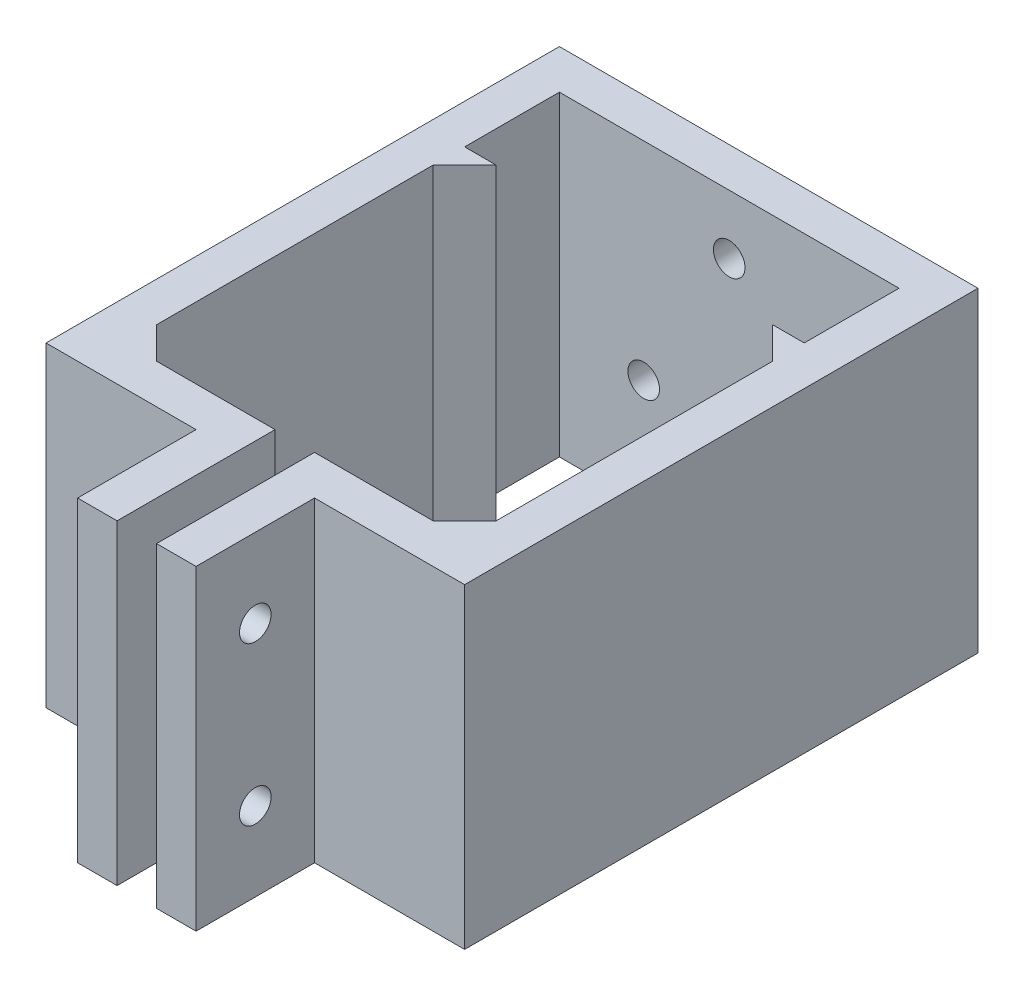
SolidWorks part; units mm, degrees
ref_plane "Спереди" through (0, 0, 0) normal (0, 0, 1) x (1, 0, 0)
ref_plane "Сверху" through (0, 0, 0) normal (0, 1, 0) x (1, 0, 0)
ref_plane "Справа" through (0, 0, 0) normal (1, 0, 0) x (0, 0, -1)
sketch "Эскиз1" plane through (0, 0, 0) normal (0, 1, 0) x (1, 0, 0)
  line L0 (0, 0) -> (0, 65)
  line L1 (0, 65) -> (53, 65)
  line L2 (53, 65) -> (53, 0)
  line L3 (53, 0) -> (34, 0)
  line L4 (34, 0) -> (34, -15)
  line L5 (34, -15) -> (29, -15)
  line L6 (29, -15) -> (29, 5)
  line L7 (29, 5) -> (48, 5)
  line L8 (48, 5) -> (48, 60)
  line L9 (48, 60) -> (5, 60)
  line L10 (5, 60) -> (5, 5)
  line L11 (5, 5) -> (24, 5)
  line L12 (24, 5) -> (24, -15)
  line L13 (24, -15) -> (19, -15)
  line L14 (19, -15) -> (19, 0)
  line L15 (19, 0) -> (0, 0)
  dimension "D1" = 55
  dimension "D2" = 5
  dimension "D3" = 43
  dimension "D4" = 5
  dimension "D5" = 5
  dimension "D6" = 53
  dimension "D7" = 5
  dimension "D8" = 15
extrude "main" add sketch "Эскиз1" along normal blind 40
chamfer "Фаска1" distance 4 angle 45 2 edges at (48, 20, -5) (5, 20, -5)
sketch "Эскиз2" plane through (0, 0, -65) normal (0, 0, -1) x (-1, 0, 0)
  line L0 (-26.5, 40) -> (-26.5, 0) construction
  line L1 (-53, 40) -> (0, 40) construction
  line L2 (-53, 0) -> (0, 0) construction
  line L3 (-53, 20) -> (0, 20) construction
  line L4 (-53, 40) -> (-53, 0) construction
  line L5 (0, 40) -> (0, 0) construction
  line L6 (-26.5, 20) -> (-37.3253, 13.75) construction
  circle A0 centre (-26.5, 20) radius 12.5 construction
  circle A1 centre (-26.5, 32.5) radius 2
  circle A2 centre (-37.3253, 13.75) radius 2
  circle A3 centre (-15.6747, 13.75) radius 2
  point P12 (-26.5, 20)
  point P15 (-26.5, 32.5)
  dimension "D1" = 25
  dimension "D2" = 4
  dimension "D3" = 120
extrude "holes" cut sketch "Эскиз2" against normal up to next
sketch "Эскиз3" plane through (0, 0, 0) normal (0, 1, 0) x (1, 0, 0)
  line L0 (5, 44) -> (5, 48)
  line L1 (5, 9) -> (5, 60) construction
  line L2 (5, 48) -> (9, 48)
  line L3 (9, 48) -> (5, 44)
  line L4 (24, 5) -> (9, 5) construction
  line L5 (26.5, 65) -> (26.5, 5) construction
  line L6 (53, 65) -> (0, 65) construction
  line L7 (44, 5) -> (29, 5) construction
  line L8 (44, 48) -> (48, 44)
  line L9 (48, 48) -> (44, 48)
  line L10 (48, 44) -> (48, 48)
  dimension "D1" = 4
  dimension "D2" = 43
extrude "Вытянуть3" add sketch "Эскиз3" along normal blind 40
sketch "Эскиз4" plane through (34, 0, 0) normal (1, 0, 0) x (0, 0, -1)
  line L0 (-7.5, 40) -> (-7.5, 0) construction
  line L1 (-15, 40) -> (0, 40) construction
  line L2 (-15, 0) -> (0, 0) construction
  circle A0 centre (-7.5, 10) radius 2
  circle A1 centre (-7.5, 30) radius 2
  dimension "D1" = 4
  dimension "D2" = 10
  dimension "D3" = 10
extrude "Вытянуть4" cut sketch "Эскиз4" against normal up to surface (15 mm away) up to face at (19, 20, 7.5)
